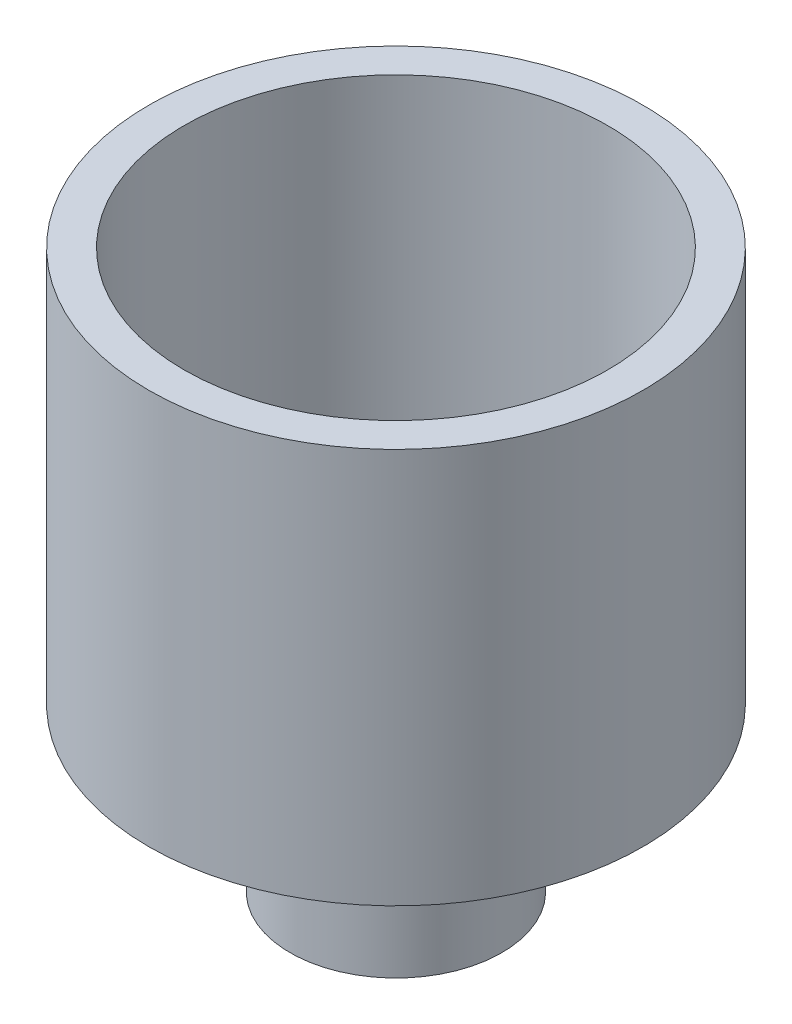
SolidWorks part; units mm, degrees
ref_plane "Front Plane" through (0, 0, 0) normal (0, 0, 1) x (1, 0, 0)
ref_plane "Top Plane" through (0, 0, 0) normal (0, 1, 0) x (1, 0, 0)
ref_plane "Right Plane" through (0, 0, 0) normal (1, 0, 0) x (0, 0, -1)
sketch "Sketch1" plane through (0, 0, 0) normal (0, 1, 0) x (1, 0, 0)
  circle A0 centre (0, 0) radius 35
  dimension "D1" = 70
extrude "Boss-Extrude1" add sketch "Sketch1" along normal blind 56
sketch "Sketch2" plane through (0, 56, 0) normal (0, 1, 0) x (1, 0, 0)
  circle A0 centre (0, 0) radius 30
  dimension "D1" = 60
extrude "Cut-Extrude1" cut sketch "Sketch2" against normal blind 46.9
sketch "Sketch3" plane through (0, 0, 0) normal (0, -1, 0) x (1, 0, 0)
  circle A0 centre (0, 0) radius 19.5
  dimension "D1" = 39
extrude "Boss-Extrude2" add sketch "Sketch3" along normal blind 7
sketch "Sketch4" plane through (0, -7, 0) normal (0, -1, 0) x (1, 0, 0)
  circle A0 centre (0, 0) radius 15
  dimension "D1" = 30
extrude "Boss-Extrude3" add sketch "Sketch4" along normal blind 16
fillet "Fillet1" radius 5 1 edges at (0, 0, -19.5)
